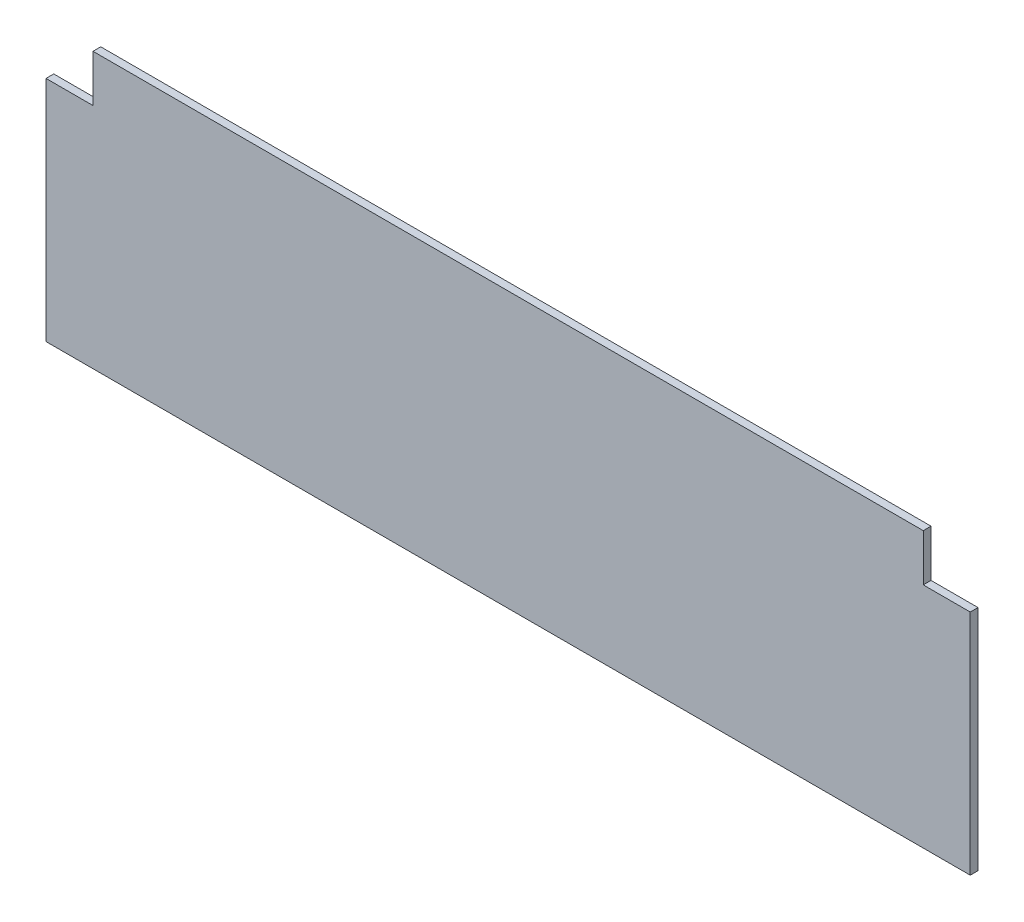
SolidWorks part; units mm, degrees
ref_plane "Front Plane" through (0, 0, 0) normal (0, 0, 1) x (1, 0, 0)
ref_plane "Top Plane" through (0, 0, 0) normal (0, 1, 0) x (1, 0, 0)
ref_plane "Right Plane" through (0, 0, 0) normal (1, 0, 0) x (0, 0, -1)
sketch "Sketch1" plane through (0, 0, 0) normal (0, 0, 1) x (1, 0, 0)
  line L0 (393.4, -136.8219) -> (393.4, -39.8043)
  line L1 (393.4, -39.8043) -> (0, -39.8043) construction
  line L2 (0, -39.8043) -> (0, -136.8219)
  line L3 (0, -136.8219) -> (393.4, -136.8219)
  line L4 (0, -138.3774) -> (0, -39.8043) construction
  line L5 (373.4, -39.8043) -> (20, -39.8043) construction
  line L6 (373.4, -39.8043) -> (373.4, -19.8043)
  line L7 (373.4, -19.8043) -> (20, -19.8043)
  line L8 (20, -39.8043) -> (20, -19.8043)
  line L9 (373.4, -39.8043) -> (20, -19.8043) construction
  line L10 (373.4, -19.8043) -> (20, -39.8043) construction
  line L13 (20.7, -19.8043) -> (372.7, -19.8043) construction
  line L14 (393.4, -39.8043) -> (393.4, -138.3812) construction
  line L18 (0, -136.8219) -> (393.4, -136.8219) construction
  line L19 (393.4, -39.8043) -> (373.4, -39.8043)
  line L20 (0, -39.8043) -> (20, -39.8043)
  point P12 (196.7, -29.8043)
  point P17 (0, 0)
  dimension "D1" = 20
  dimension "D2" = 20
  dimension "D3" = 20
extrude "Boss-Extrude1" add sketch "Sketch1" against normal blind 3.3 contours L2 L3 L0 L1 | L8 L1 L6 L7 region at (196.7, -79.171, 0)
